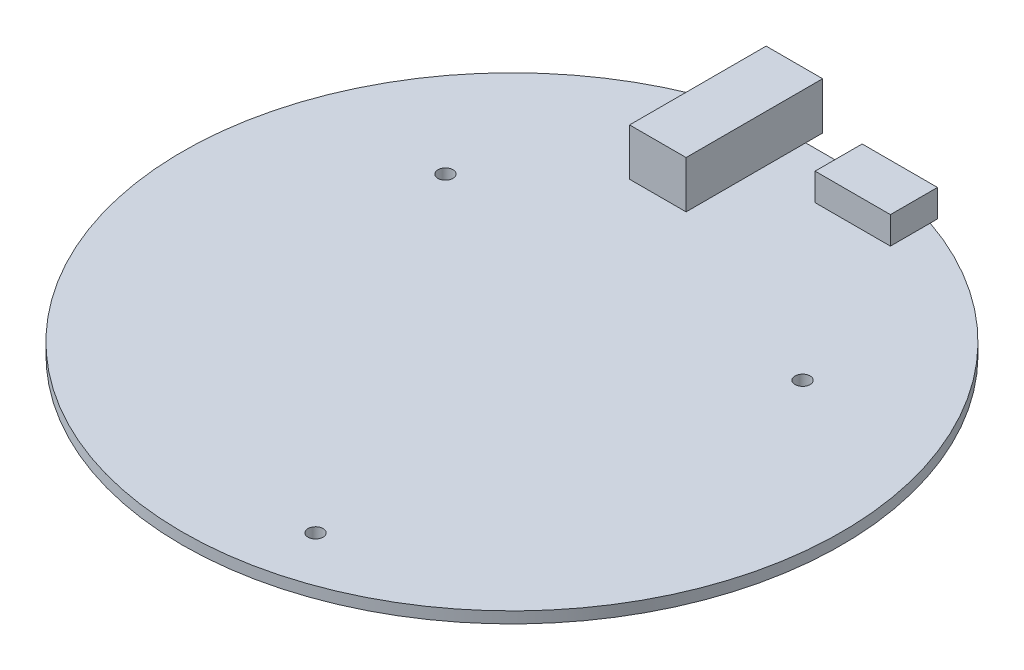
SolidWorks part; units mm, degrees
ref_plane "Front Plane" through (0, 0, 0) normal (0, 0, 1) x (1, 0, 0)
ref_plane "Top Plane" through (0, 0, 0) normal (0, 1, 0) x (1, 0, 0)
ref_plane "Right Plane" through (0, 0, 0) normal (1, 0, 0) x (0, 0, -1)
sketch "Sketch1" plane through (0, 0, 0) normal (0, 1, 0) x (1, 0, 0)
  line L0 (0, -35) -> (0, 33.9) construction
  line L1 (-8.7057, 33.9) -> (8.7057, 33.9)
  line L2 (0, 33.9) -> (0, 11.9) construction
  line L3 (0, 0) -> (18.9638, 11.9) construction
  line L4 (0, 11.9) -> (18.9638, 11.9) construction
  line L5 (0, -35) -> (0, -28) construction
  line L6 (0, -28) -> (7.14, -28) construction
  line L8 (-8.7057, 33.9) -> (-8.7057, 35.7) construction
  line L9 (-8.7057, 35.7) -> (-2.7057, 35.7) construction
  line L10 (-8.7057, 33.9) -> (-8.7057, 35.7)
  line L11 (-8.7057, 35.7) -> (-2.7057, 35.7)
  line L12 (-2.7057, 35.7) -> (-2.7057, 33.9)
  line L13 (-8.7057, 33.9) -> (-8.7057, 21.2)
  line L14 (-2.7057, 33.9) -> (-2.7057, 21.2)
  line L15 (-8.7057, 21.2) -> (-2.7057, 21.2)
  line L18 (-2.7057, 33.9) -> (3.8943, 33.9)
  arc A1 (-8.7057, 33.9) -> (8.7057, 33.9) centre (0, 0) ccw
  circle A2 centre (18.9638, 11.9) radius 0.8
  circle A3 centre (-18.9638, 11.9) radius 0.8
  circle A4 centre (7.14, -28) radius 0.8
  dimension "D1" = 35
  dimension "D6" = 1.6
  dimension "D10" = 1.6
  dimension "D2" = 68.9
  dimension "D3" = 17.4115
  dimension "D4" = 22
  dimension "D5" = 22.3883
  dimension "D7" = 7
  dimension "D8" = 7.14
  dimension "D11" = 1.8
  dimension "D12" = 6
  dimension "D13" = 12.7
  dimension "D16" = 6.6
extrude "Boss-Extrude1" add sketch "Sketch1" along normal blind 5 contours L13 L15 L14 L12 L11 L10
extrude "Boss-Extrude3" add sketch "Sketch1<4>" against normal blind 1.2 contours L13 A1 L1 L14 L15 A4 A2 A3 | L13 L15 L14 L1 region at (-5.7057, 0, -27.55) region at (0.112, 0, 0.6743)
sketch "Sketch1<4>" plane through (0, 0, 0) normal (0, 1, 0) x (1, 0, 0) same geometry as "Sketch1"
sketch "Sketch4" plane through (0, 0, 0) normal (0, 1, 0) x (1, 0, 0)
  line L0 (-2.7057, 33.9) -> (3.2943, 33.9)
  line L1 (-8.7057, 33.9) -> (8.7057, 33.9) construction
  line L2 (3.2943, 33.9) -> (3.2943, 28.9)
  line L3 (3.2943, 28.9) -> (11.2943, 28.9)
  line L4 (3.2943, 33.9) -> (11.2943, 33.9)
  line L5 (11.2943, 33.9) -> (11.2943, 28.9)
  line L6 (0, 33.9) -> (0, 0) construction
  line L7 (3.2943, 33.9) -> (11.2943, 33.9)
  dimension "D1" = 8
  dimension "D2" = 5
  dimension "D3" = 6
extrude "Boss-Extrude5" add sketch "Sketch4" along normal blind 2.9 contours L5 L4 L2 L3 region at (7.2943, 0, -31.4)
